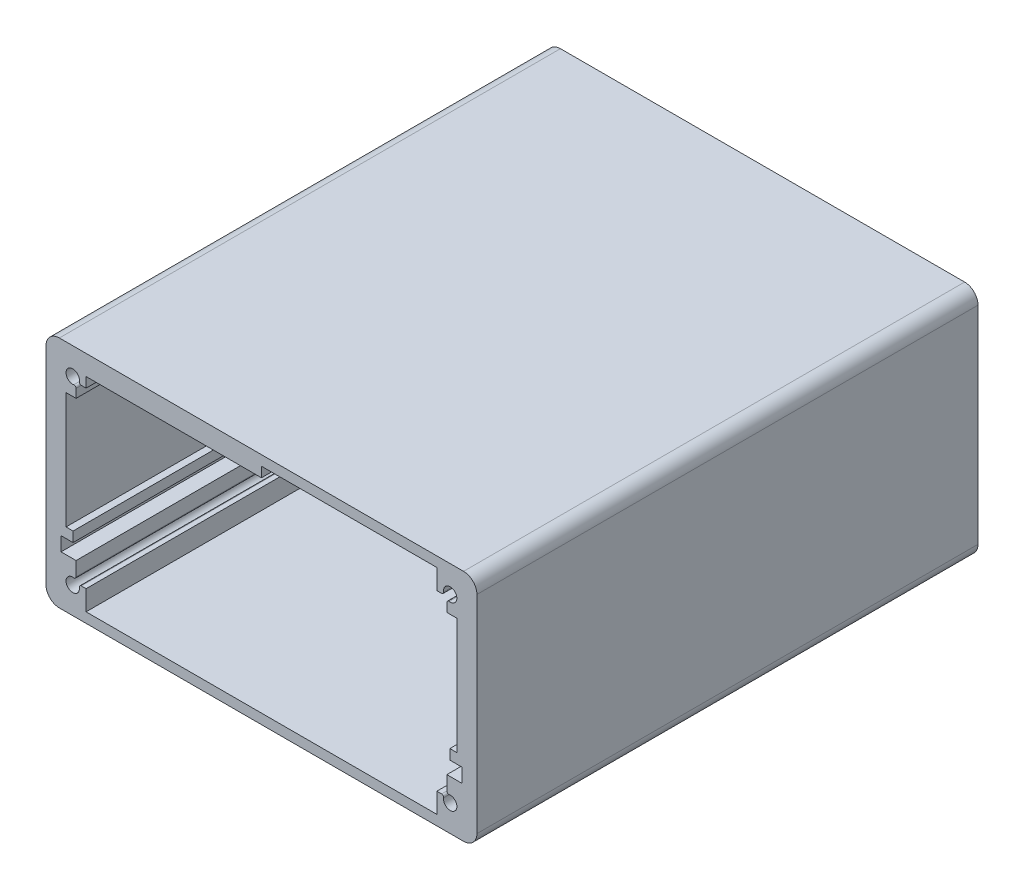
SolidWorks part; units mm, degrees
material "201 Acier inoxydable recuit (SS)"
ref_plane "Plan de face" through (0, 0, 0) normal (0, 0, 1) x (1, 0, 0)
ref_plane "Plan de dessus" through (0, 0, 0) normal (0, 1, 0) x (1, 0, 0)
ref_plane "Plan de droite" through (0, 0, 0) normal (1, 0, 0) x (0, 0, -1)
ref_axis "Axe OZ" through (0, 0, -87.49) along (0, 0, 1)
sketch "Sketch1" plane through (0, 0, 0) normal (0, 0, 1) x (1, 0, 0)
  line L1 (-32.25, 17.5) -> (32.25, 17.5)
  line L2 (-32.25, 17.5) -> (-32.25, -17.5)
  line L3 (-32.25, -17.5) -> (32.25, -17.5)
  line L4 (32.25, 17.5) -> (32.25, -17.5)
  line L5 (-32.25, 17.5) -> (32.25, -17.5) construction
  line L6 (-32.25, -17.5) -> (32.25, 17.5) construction
  point P0 (0, 0)
  dimension "D1" = 35
  dimension "D2" = 64.5
extrude "Boss-Extrude1" add sketch "Sketch1" along normal blind 75
fillet "Fillet1" radius 2 4 edges at (-32.25, -17.5, 37.5) (32.25, -17.5, 37.5) (32.25, 17.5, 37.5) (-32.25, 17.5, 37.5)
sketch "Sketch2" plane through (0, 0, 75) normal (0, 0, 1) x (1, 0, 0)
  line L16 (-28.25, 13.5) -> (28.25, 13.5) construction
  line L17 (-28.25, 13.5) -> (-28.25, -13.5) construction
  line L18 (-28.25, -13.5) -> (28.25, -13.5) construction
  line L19 (28.25, 13.5) -> (28.25, -13.5) construction
  line L20 (-28.25, 13.5) -> (28.25, -13.5) construction
  line L21 (-28.25, -13.5) -> (28.25, 13.5) construction
  circle A4 centre (-28.25, 13.5) radius 1
  circle A5 centre (-28.25, -13.5) radius 1
  circle A6 centre (28.25, -13.5) radius 1
  circle A7 centre (28.25, 13.5) radius 1
  point P5 (0, 0)
  dimension "D2" = 2
  dimension "D3" = 27
  dimension "D4" = 56.5
extrude "fix" cut sketch "Sketch2" against normal through all
sketch "Sketch3" plane through (0, 0, 75) normal (0, 0, 1) x (1, 0, 0)
  line L0 (-27.75, 10.92) -> (-27.75, 13)
  line L1 (-27.75, 13) -> (-26.25, 13)
  line L2 (-26.25, 13) -> (-26.25, 14.5)
  line L3 (-26.25, 14.5) -> (0, 14.5)
  line L4 (-27.75, 10.92) -> (-29.25, 10.92)
  line L5 (-29.25, 10.92) -> (-29.25, -6.5)
  line L6 (0, 0) -> (0, 8.9891) construction
  line L7 (0, 0) -> (8.6464, 0) construction
  line L8 (29.25, 10.92) -> (29.25, -6.5)
  line L9 (27.75, 10.92) -> (29.25, 10.92)
  line L10 (26.25, 14.5) -> (0, 14.5)
  line L11 (26.25, 13) -> (26.25, 14.5)
  line L12 (27.75, 13) -> (26.25, 13)
  line L13 (27.75, 10.92) -> (27.75, 13)
  line L14 (27.75, -6.5) -> (27.75, -13)
  line L15 (27.75, -13) -> (26.25, -13)
  line L16 (26.25, -13) -> (26.25, -14.5)
  line L17 (26.25, -14.5) -> (0, -14.5)
  line L22 (-26.25, -14.5) -> (0, -14.5)
  line L23 (-26.25, -13) -> (-26.25, -14.5)
  line L24 (-27.75, -13) -> (-26.25, -13)
  line L25 (-27.75, -6.5) -> (-27.75, -13)
  line L26 (-32.25, 15.5) -> (-32.25, -15.5) construction
  line L27 (30.25, 17.5) -> (-30.25, 17.5) construction
  line L28 (27.75, -6.5) -> (29.25, -6.5)
  line L29 (-30.25, -17.5) -> (30.25, -17.5) construction
  line L30 (-29.25, -6.5) -> (-27.75, -6.5)
  point P15 (-27.75, 11.96)
  point P35 (-26.25, 13.75)
  dimension "D1" = 4.5
  dimension "D2" = 4.5
  dimension "D3" = 3
  dimension "D4" = 3
  dimension "D5" = 17.42
  dimension "D6" = 11
  dimension "D7" = 6
extrude "Cut-Extrude2" cut sketch "Sketch3" against normal blind 75
sketch "Sketch4" plane through (0, 0, 75) normal (0, 0, 1) x (1, 0, 0)
  line L0 (0, 0) -> (0, 8.0206) construction
  line L1 (-30, -8) -> (-28.2, -8)
  line L2 (-30, -8) -> (-30, -10.1)
  line L3 (-30, -10.1) -> (30, -10.1)
  line L4 (30, -8) -> (30, -10.1)
  line L5 (-30.25, -17.5) -> (30.25, -17.5) construction
  line L6 (-28.2, -8) -> (-28.2, -4.9906)
  line L7 (-28.2, -4.9906) -> (28.2, -5.3712)
  line L8 (28.2, -5.3712) -> (28.2, -8)
  line L9 (28.2, -8) -> (30, -8)
  dimension "D1" = 2.1
  dimension "D2" = 60
  dimension "D3" = 7.4
  dimension "D4" = 56.4
extrude "Cut-Extrude3" cut sketch "Sketch4" against normal blind 75
sketch "Sketch5" plane through (0, 0, 75) normal (0, 0, 1) x (1, 0, 0)
  line L0 (26.25, 14.5) -> (-26.25, 14.5) construction
  line L1 (26.25, 14.5) -> (0, 14.5)
  line L2 (26.25, 14.5) -> (26.25, 16)
  line L3 (26.25, 16) -> (0, 16)
  line L4 (0, 14.5) -> (0, 16)
  line L5 (26.25, 13) -> (26.25, 14.5) construction
  dimension "D1" = 1.5
extrude "Cut-Extrude4" cut sketch "Sketch5" against normal blind 75
sketch "Sketch6" plane through (0, 0, 75) normal (0, 0, 1) x (1, 0, 0)
  line L0 (26.25, -14.5) -> (26.25, -13) construction
  line L1 (26.25, -16) -> (-26.25, -16)
  line L2 (26.25, -16) -> (26.25, -14.5)
  line L3 (26.25, -14.5) -> (-26.25, -14.5)
  line L4 (-26.25, -16) -> (-26.25, -14.5)
  line L5 (-26.25, -14.5) -> (26.25, -14.5) construction
  dimension "D1" = 1.5
fillet "Fillet2" radius 0.3 8 edges at (27.384, 13, 37.5) (27.75, 12.634, 37.5) (-27.384, 13, 37.5) (-27.75, 12.634, 37.5) (-27.75, -12.634, 37.5) (-27.384, -13, 37.5) (27.384, -13, 37.5) (27.75, -12.634, 37.5)
extrude "bas" cut sketch "Sketch6" against normal through all
